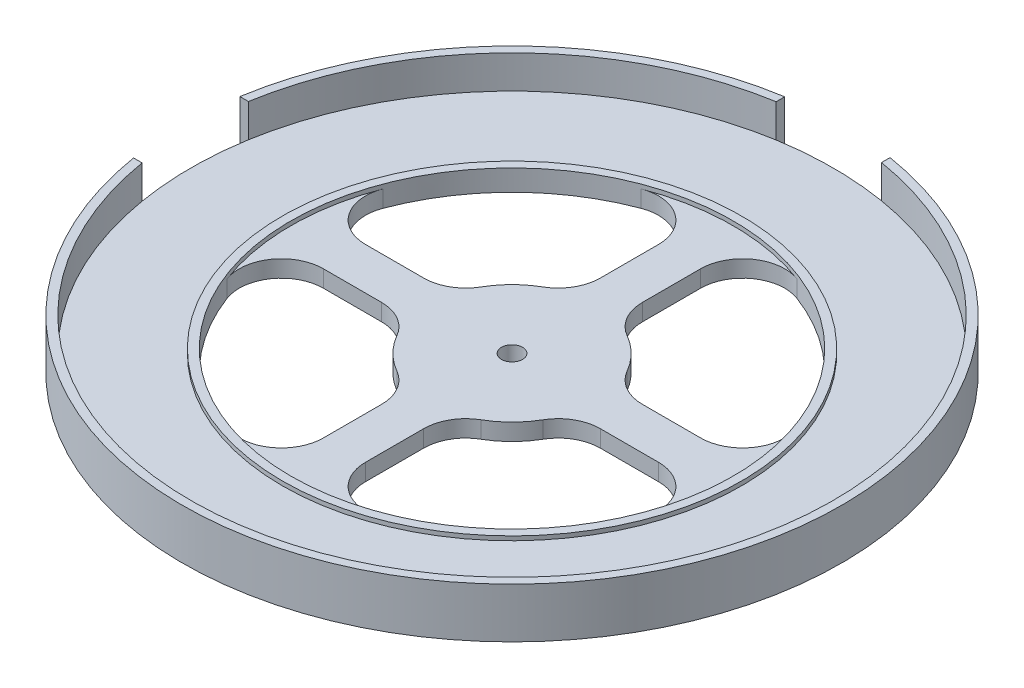
SolidWorks part; units mm, degrees
ref_plane "Front Plane" through (0, 0, 0) normal (0, 0, 1) x (1, 0, 0)
ref_plane "Top Plane" through (0, 0, 0) normal (0, 1, 0) x (1, 0, 0)
ref_plane "Right Plane" through (0, 0, 0) normal (1, 0, 0) x (0, 0, -1)
sketch "Sketch1" plane through (0, 0, 0) normal (0, 1, 0) x (1, 0, 0)
  line L0 (0, 109) -> (0, -109) construction
  line L1 (-109, 0) -> (109, 0) construction
  line L6 (-10, 104.5227) -> (-10, -104.5227)
  line L7 (-104.5227, -10) -> (104.5227, -10)
  line L16 (10, 104.5227) -> (10, -104.5227)
  line L17 (-104.5227, 10) -> (104.5227, 10)
  line L18 (-109, 10) -> (109, 10) construction
  line L19 (-109, -10) -> (109, -10) construction
  line L20 (10, 109) -> (10, -109) construction
  line L21 (-10, 109) -> (-10, -109) construction
  line L22 (-25, 150.4369) -> (25, 150.4369) construction
  line L24 (-25, 150.4369) -> (-25, 154.4903)
  line L26 (25, 150.4369) -> (25, 154.4903)
  line L29 (-154.4499, -25.2483) -> (-150.3954, -25.2483)
  line L31 (-154.4499, 25.2483) -> (-150.3954, 25.2483)
  arc A9 (-154.4499, -25.2483) -> (25, 154.4903) centre (0, 0) ccw
  circle A10 centre (0, 0) radius 109
  circle A12 centre (0, 0) radius 152.5
  circle A13 centre (0, 0) radius 105
  arc A14 (-25, 154.4903) -> (-154.4499, 25.2483) centre (0, 0) ccw
  circle A15 centre (0, 0) radius 5
  point P18 (0, 131.7764)
  point P31 (-134.7515, 0)
  dimension "D1" = 313
  dimension "D2" = 305
  dimension "D5" = 10
  dimension "D6" = 210
  dimension "D3" = 218
  dimension "D7" = 50
  dimension "D8" = 10
  dimension "D4" = 10
extrude "Boss-Extrude3" add sketch "Sketch1" along normal blind 8 contours A12 A10 | L17 A13 L7 L6 | L6 A13 L16 L7 | L7 A13 L17 L16 | L16 A13 L6 L17 | L17 L6 L7 L16 region at (0, 0, -57.4206) region at (0, 0, -9.7172) region at (-57.4206, 0, 0) region at (0, 0, 57.4206) region at (57.4206, 0, 0) region at (0, 0, -148.1866)
extrude "Boss-Extrude4" add sketch "Sketch1<8>" along normal blind 23.75 contours A9 A12 region at (29.3978, 0, -152.4636)
sketch "Sketch1<8>" plane through (0, 0, 0) normal (0, 1, 0) x (1, 0, 0) same geometry as "Sketch1"
extrude "Boss-Extrude5" add sketch "Sketch1<9>" along normal blind 10 contours A10 A13 region at (-105.917, 0, 0)
sketch "Sketch1<9>" plane through (0, 0, 0) normal (0, 1, 0) x (1, 0, 0) same geometry as "Sketch1"
extrude "Boss-Extrude6" add sketch "Sketch1<10>" along normal blind 23.75 contours L24 A14 L31 A12 region at (-109.0371, 0, -109.2173)
sketch "Sketch1<10>" plane through (0, 0, 0) normal (0, 1, 0) x (1, 0, 0) same geometry as "Sketch1"
sketch "Sketch2" plane through (0, 8, 0) normal (0, 1, 0) x (1, 0, 0)
  circle A0 centre (0, 0) radius 40
  circle A1 centre (0, 0) radius 5
  dimension "D1" = 80
extrude "Boss-Extrude7" add sketch "Sketch2" against normal up to surface (8 mm away) up to face at (-47.1692, 0, 47.1692)
fillet "Fillet1" radius 20 16 edges at (10, 4, -38.7298) (-38.7298, 4, -10) (-104.5227, 4, -10) (10, 4, 104.5227) (-10, 4, 104.5227) (104.5227, 4, 10) (104.5227, 4, -10) (-10, 4, 38.7298) (-38.7298, 4, 10) (-104.5227, 4, 10) (10, 4, 38.7298) (38.7298, 4, 10) (38.7298, 4, -10) (10, 4, -104.5227) (-10, 4, -104.5227) (-10, 4, -38.7298)
